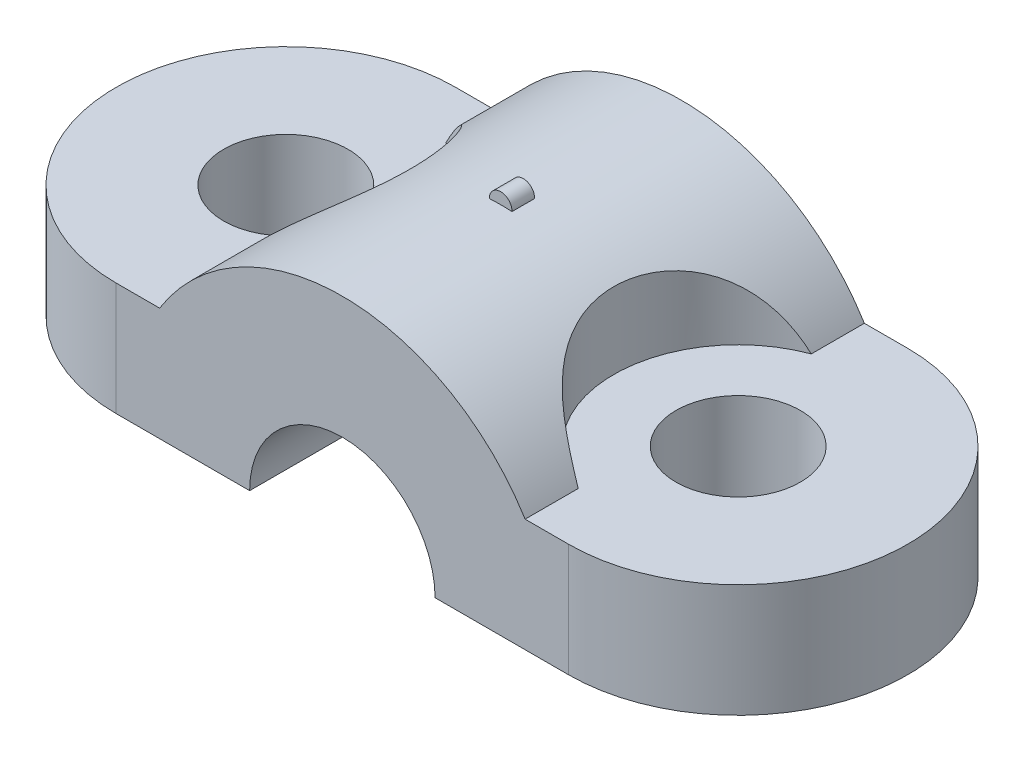
SolidWorks part; units mm, degrees
ref_plane "Front Plane" through (0, 0, 0) normal (0, 0, 1) x (1, 0, 0)
ref_plane "Top Plane" through (0, 0, 0) normal (0, 1, 0) x (1, 0, 0)
ref_plane "Right Plane" through (0, 0, 0) normal (1, 0, 0) x (0, 0, -1)
sketch "Sketch1" plane through (0, 0, 0) normal (0, 1, 0) x (1, 0, 0)
  line L0 (-10, 7.5) -> (10, 7.5)
  line L1 (-10, -7.5) -> (10, -7.5)
  line L2 (-8.08, 7.5) -> (-8.08, 5.154)
  line L3 (-8.08, -5.154) -> (-8.08, -7.5)
  line L4 (8.08, -7.5) -> (8.08, -5.154)
  line L5 (8.08, 7.5) -> (8.08, 5.154)
  circle A0 centre (-10, 0) radius 2.75
  circle A1 centre (10, 0) radius 2.75
  circle A2 centre (-10, 0) radius 5.5
  circle A3 centre (10, 0) radius 5.5
  circle A4 centre (-10, 0) radius 7.5
  circle A5 centre (10, 0) radius 7.5
  point P21 (0, 7.5)
  dimension "D1" = 5.5
  dimension "D2" = 2.75
  dimension "D3" = 4.75
  dimension "D4" = 20
  dimension "D5" = 10
  dimension "D6" = 8.08
  dimension "D7" = 8.08
extrude "Boss-Extrude1" add sketch "Sketch1" along normal blind 9.5 contours A5 L5 L0 L2 A4 L3 L1 L4 | L3 A4 L2 A2 | L5 A5 L4 A3 region at (0, 0, 0) region at (-4.1796, 0, -4.4796) region at (7.9246, 0, -6.202)
extrude "Boss-Extrude2" add sketch "Sketch1<3>" along normal blind 5 contours A2 A0 | A4 L3 A2 L2 | A3 A1 | A5 L5 A3 L4 | A4 L2 L0 | A4 L1 L3 | A5 L4 L1 | A5 L0 L5 region at (-9.0548, 0, -7.2616) region at (-8.5584, 0, -7.4252) region at (-8.5584, 0, 7.4252) region at (8.5584, 0, -7.4252) region at (-5.6106, 0, -3.0489) region at (15.1781, 0, -5.1781) region at (8.5584, 0, 7.4252) region at (13.0489, 0, -4.3894)
sketch "Sketch1<3>" plane through (0, 0, 0) normal (0, 1, 0) x (1, 0, 0) same geometry as "Sketch1"
sketch "Sketch3" plane through (0, 0, 7.5) normal (0, 0, 1) x (1, 0, 0)
  line L0 (-10, 0) -> (10, 0) construction
  line L3 (-8.08, 9.5) -> (-8.08, 5) construction
  line L4 (-8.08, 9.5) -> (8.08, 9.5) construction
  line L5 (8.08, 9.5) -> (8.08, 5) construction
  line L6 (-8.08, 9.5) -> (-8.08, 5)
  line L7 (-8.08, 9.5) -> (8.08, 9.5)
  line L8 (8.08, 9.5) -> (8.08, 5)
  circle A0 centre (0, 0) radius 4.1
  arc A1 (-8.08, 5) -> (8.08, 5) centre (0, -0.004) cw
  point P6 (0, 0)
  line M1 (-10, 0) -> (10, 0)
  line M4 (8.08, 9.5) -> (-8.08, 9.5)
  line M10 (8.08, 5) -> (8.08, 9.5)
  line M11 (-8.08, 9.5) -> (-8.08, 5)
  dimension "D2" = 8.2
  dimension "D1" = 0
extrude "Cut-Extrude2" cut sketch "Sketch3" against normal through all contours A1 L7 M11 | A1 M4 M10 | A0 M1 region at (-6.1679, 8.2305, 7.5) region at (6.1679, 8.2305, 7.5) region at (0, 1.7401, 7.5)
sketch "Sketch5" plane through (0, 5, 0) normal (0, 1, 0) x (1, 0, 0)
  line L0 (-17.5, 0) -> (17.5, 0) construction
  arc A0 (-10, 7.5) -> (-10, -7.5) centre (-10, 0) ccw construction
  arc A1 (10, -7.5) -> (10, 7.5) centre (10, 0) ccw construction
sketch "Sketch6" plane through (0, 0, 0) normal (0, -1, 0) x (1, 0, 0)
  line L0 (-17.5, 0) -> (17.5, 0) construction
  arc A0 (-10, 7.5) -> (-10, -7.5) centre (-10, 0) ccw construction
  arc A1 (10, -7.5) -> (10, 7.5) centre (10, 0) ccw construction
sketch3d "3DSketch1"
  line L0 (-17.5, 0, 0) -> (17.5, 0, 0) construction
  line L1 (-17.5, 5, 0) -> (17.5, 5, 0) construction
sketch "Sketch7" plane through (0, 0, 0) normal (0, 0, 1) x (1, 0, 0)
  line L0 (0, 0) -> (0, 15.6574) construction
  arc A0 (8.08, 5) -> (-8.08, 5) centre (0, -0.004) ccw construction
  arc A1 (8.08, 5) -> (-8.08, 5) centre (0, -0.004) ccw
  circle A2 centre (0, 9.5) radius 0.5
  dimension "D1" = 1
extrude "Boss-Extrude3" add sketch "Sketch7" along normal mid plane 1 contours A1 L0 A2 | L0 A1 A2 region at (-0.214, 9.7098, 0) region at (0.214, 9.7098, 0)
